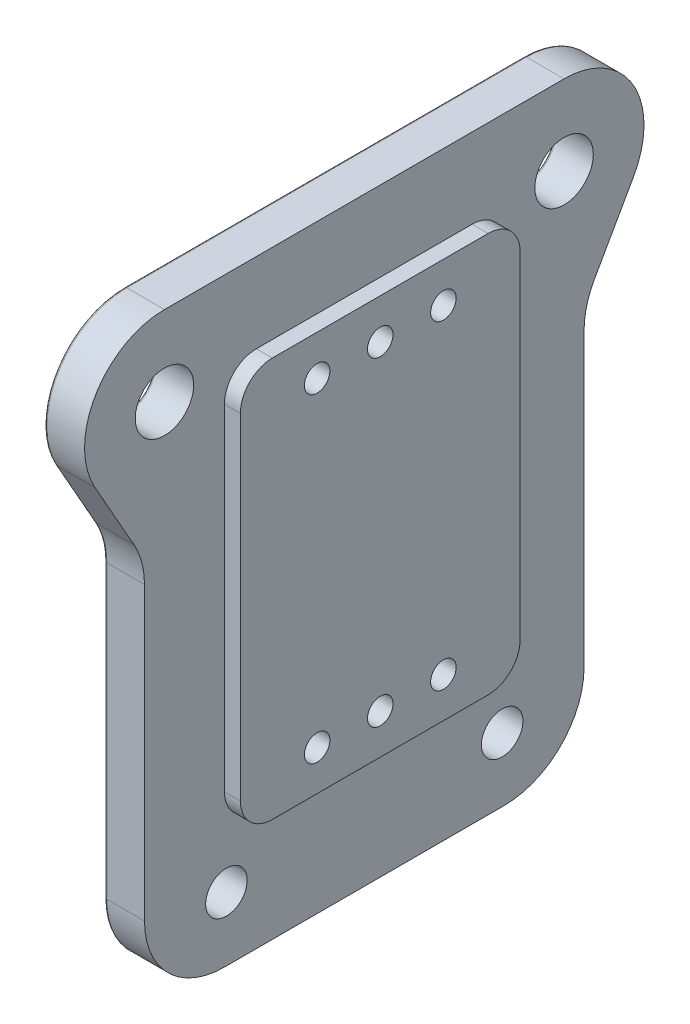
SolidWorks part; units mm, degrees
note: The reader was unsure of these and kept them because the rebuilt part matched: shared geometry of "Эскиз2<3>".
ref_plane "Спереди (Плоскость XY)" through (0, 0, 0) normal (0, 0, 1) x (1, 0, 0)
ref_plane "Сверху (Плоскость XZ)" through (0, 0, 0) normal (0, 1, 0) x (1, 0, 0)
ref_plane "Справа (Плоскость ZY)" through (0, 0, 0) normal (1, 0, 0) x (0, 0, -1)
sketch "Эскиз2" plane through (0, 0, 0) normal (1, 0, 0) x (0, 0, -1)
  line L0 (-17.5, -29.4427) -> (17.5, -29.4427)
  line L1 (-25, 45.5573) -> (25, 45.5573)
  line L2 (-17.5, 10.5573) -> (17.5, 10.5573) construction
  line L3 (0, -168.396) -> (0, 124.0583) construction
  line L24 (-13.5, -14.4427) -> (13.5, -14.4427)
  line L25 (-17.5, -10.4427) -> (-17.5, 31.5573)
  line L26 (-13.5, 35.5573) -> (13.5, 35.5573)
  line L27 (17.5, -10.4427) -> (17.5, 31.5573)
  line L30 (27.5, 17.0241) -> (27.5, -19.4427)
  line L31 (33.7063, 30.6379) -> (28.7937, 21.9435)
  line L32 (-27.5, 17.0241) -> (-27.5, -19.4427)
  line L33 (-33.7063, 30.6379) -> (-28.7937, 21.9435)
  circle A4 centre (17.25, -21.4427) radius 2.6
  circle A5 centre (-17.25, -21.4427) radius 2.6
  circle A7 centre (-25, 35.5573) radius 3.655
  circle A12 centre (25, 35.5573) radius 3.655
  circle A23 centre (7.9, -9.4427) radius 1.6
  circle A24 centre (-7.9, 30.5573) radius 1.6
  circle A27 centre (7.9, 30.5573) radius 1.6
  circle A28 centre (0, 30.5573) radius 1.6
  arc A30 (13.5, -14.4427) -> (17.5, -10.4427) centre (13.5, -10.4427) ccw
  arc A31 (-13.5, -14.4427) -> (-17.5, -10.4427) centre (-13.5, -10.4427) cw
  arc A32 (13.5, 35.5573) -> (17.5, 31.5573) centre (13.5, 31.5573) cw
  arc A33 (-17.5, 31.5573) -> (-13.5, 35.5573) centre (-13.5, 31.5573) cw
  arc A36 (35, 35.5573) -> (25, 45.5573) centre (25, 35.5573) ccw
  circle A38 centre (0, -9.4427) radius 1.6
  circle A39 centre (-7.9, -9.4427) radius 1.6
  arc A41 (27.5, -19.4427) -> (17.5, -29.4427) centre (17.5, -19.4427) cw
  arc A42 (33.7063, 30.6379) -> (35, 35.5573) centre (25, 35.5573) ccw
  arc A45 (27.5, 17.0241) -> (28.7937, 21.9435) centre (37.5, 17.0241) cw
  arc A46 (-35, 35.5573) -> (-25, 45.5573) centre (-25, 35.5573) cw
  arc A47 (-33.7063, 30.6379) -> (-35, 35.5573) centre (-25, 35.5573) cw
  arc A48 (-27.5, 17.0241) -> (-28.7937, 21.9435) centre (-37.5, 17.0241) ccw
  arc A49 (-27.5, -19.4427) -> (-17.5, -29.4427) centre (-17.5, -19.4427) ccw
  point P12 (31.25, 26.2907)
  point P31 (-17.5, -14.4427)
  point P34 (17.5, 35.5573)
  point P39 (-17.5, 35.5573)
  point P63 (40, -34.5335)
  point P66 (0, 45.5573)
  point P75 (27.5, 19.6539)
  point P77 (0, -29.4427)
  point P78 (-31.25, 26.2907)
  dimension "D2" = 40
  dimension "D3" = 5.2
  dimension "D4" = 15.8
  dimension "D10" = 57
  dimension "D18" = 7.31
  dimension "D5" = 10
  dimension "D9" = 4
  dimension "D11" = 34.5
  dimension "D14" = 3.2
  dimension "D6" = 75
  dimension "D7" = 35
  dimension "D8" = 50
  dimension "D12" = 15
  dimension "D13" = 50
extrude "Бобышка-Вытянуть1" add sketch "Эскиз2" along normal blind 5
extrude "Бобышка-Вытянуть2" add sketch "Эскиз2<3>" along normal blind 2 from surface at 5 contours L24 L3 A23 A28 L26 A33 L25 A31 A24 A38 | L3 L24 A30 L27 A32 L26 A28 A23 A39 A27
sketch "Эскиз2<3>" plane through (0, 0, 0) normal (1, 0, 0) x (0, 0, -1) same geometry as "Эскиз2"
fillet "Скругление2" radius 0.3 16 edges at (0, -21.4427, -19.85) (0, 35.5573, -28.655) (0, 35.5573, 21.345) (0, -21.4427, 14.65) (0, 40.5974, -33.6369) (0, 45.5573, 0) (0, -29.4427, 0) (0, 26.2907, -31.25) (0, 19.5674, -27.8288) (0, -1.2093, -27.5) (0, -26.5138, -24.5711) (0, 40.5974, 33.6369) (0, -26.5138, 24.5711) (0, -1.2093, 27.5) (0, 19.5674, 27.8288) (0, 26.2907, 31.25)
equation "\"deltahole\"= 0.2"
